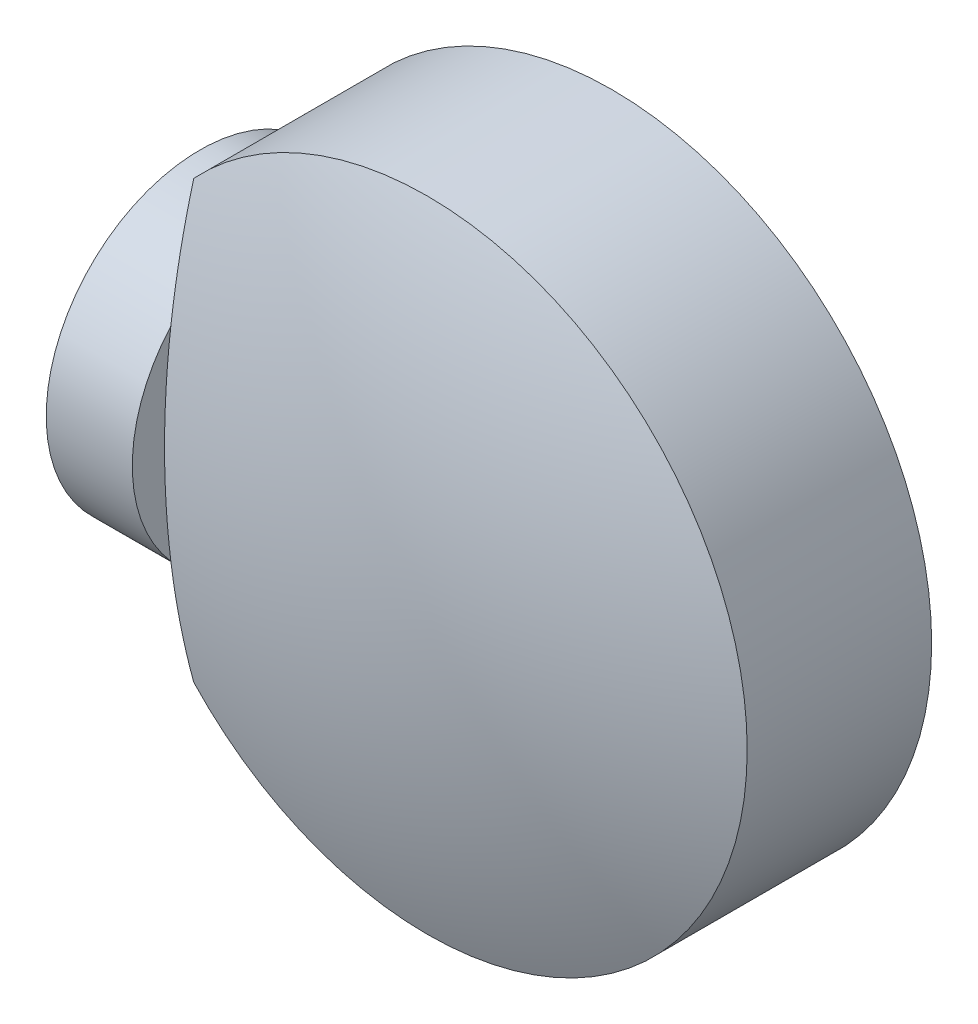
SolidWorks part; units mm, degrees
ref_plane "Plan de face" through (0, 0, 0) normal (0, 0, 1) x (1, 0, 0)
ref_plane "Plan de dessus" through (0, 0, 0) normal (0, 1, 0) x (1, 0, 0)
ref_plane "Plan de droite" through (0, 0, 0) normal (1, 0, 0) x (0, 0, -1)
sketch "Esquisse1" plane through (0, 0, 0) normal (0, 0, 1) x (1, 0, 0)
  circle A0 centre (0, 0) radius 26
extrude "Extrusion1" add sketch "Esquisse1" along normal blind 15
dome "Dôme1" faces to dome 1 distance 5 reverse direction no elliptical dome no face at (26, 0, 15) parameters "D1"=5
dome "Dôme2" faces to dome 1 distance 5 reverse direction no elliptical dome no face at (26, 0, 0) parameters "D1"=5
sketch "Esquisse2" plane through (0, 0, 0) normal (0, 0, 1) x (1, 0, 0)
  line L1 (-19, 32.096) -> (-35.8975, 32.096)
  line L2 (-19, 32.096) -> (-19, -30.385)
  line L3 (-19, -30.385) -> (-35.8975, -30.385)
  line L4 (-35.8975, 32.096) -> (-35.8975, -30.385)
  circle A0 centre (0, 0) radius 26 construction
  dimension "D1" = 19
extrude "Extrusion2" cut sketch "Esquisse2" against normal through all and the other way through all
sketch "Esquisse3" plane through (-19, 0, 0) normal (-1, 0, 0) x (0, 0, 1)
  line L0 (0, 17.7482) -> (15, 17.7482) construction
  line L1 (7.5, 17.7482) -> (7.5, -17.7482) construction
  line L2 (15, -17.7482) -> (0, -17.7482) construction
  circle A0 centre (7.5, -0.0018) radius 12.5
  dimension "D1" = 17.75
  dimension "D2" = 0
extrude "Extrusion3" add sketch "Esquisse3" along normal blind 7
